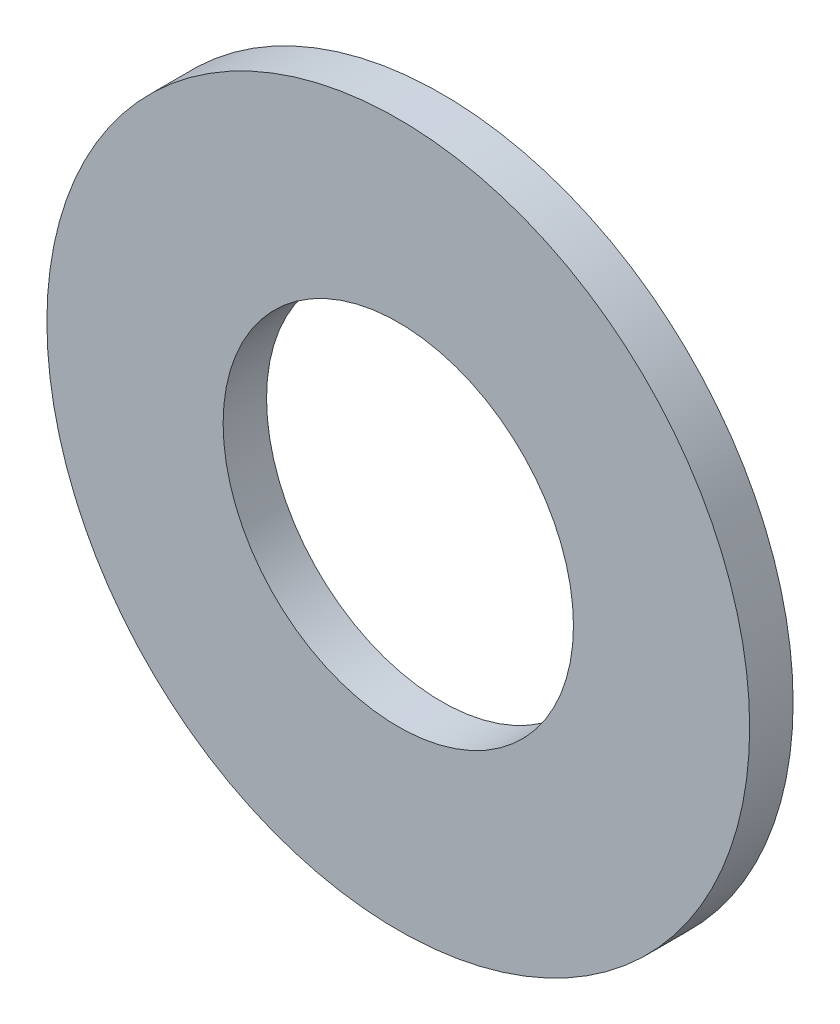
SolidWorks part; units mm, degrees
other "Imported1"
material "PTFE (general)"
ref_plane "Front Plane" through (0, 0, 0) normal (0, 0, 1) x (1, 0, 0)
ref_plane "Top Plane" through (0, 0, 0) normal (0, 1, 0) x (1, 0, 0)
ref_plane "Right Plane" through (0, 0, 0) normal (1, 0, 0) x (0, 0, -1)
sketch "Sketch1" plane through (0, 0, 0) normal (0, 0, 1) x (1, 0, 0)
  line L0 (-12.7381, 0) -> (12.7381, 0) construction
  line L1 (-6.35, 0) -> (6.35, 0) construction
  circle A0 centre (0, 0) radius 6.35 construction
  circle A1 centre (0, 0) radius 12.7381 construction
  point P8 (0, 0)
  point P9 (0, 12.7381)
  point P11 (6.35, 0)
  dimension "ID" = 12.7
  dimension "OD" = 25.4762
sketch "Sketch2" plane through (0, 0, 0) normal (1, 0, 0) x (0, 0, -1)
  line L0 (-0.7874, 12.7381) -> (0.7874, 12.7381) construction
  point P2 (0, 12.7381)
  dimension "Thickness" = 1.5748
sketch "Sketch3" plane through (0, 0, 0) normal (0, 0, 1) x (1, 0, 0)
  circle A0 centre (0, 0) radius 6.35
  circle A1 centre (0, 0) radius 12.7381
extrude "Boss-Extrude1" add sketch "Sketch3" along normal up to vertex (0.7874 mm away) and the other way up to vertex (0.7874 mm away) up to point (0, 12.7381, 0.7874) other way up to point (0, 12.7381, -0.7874)
ref_axis "Center Axis 1" through (0, 0, 0.7874) along (0, 0, -1)
